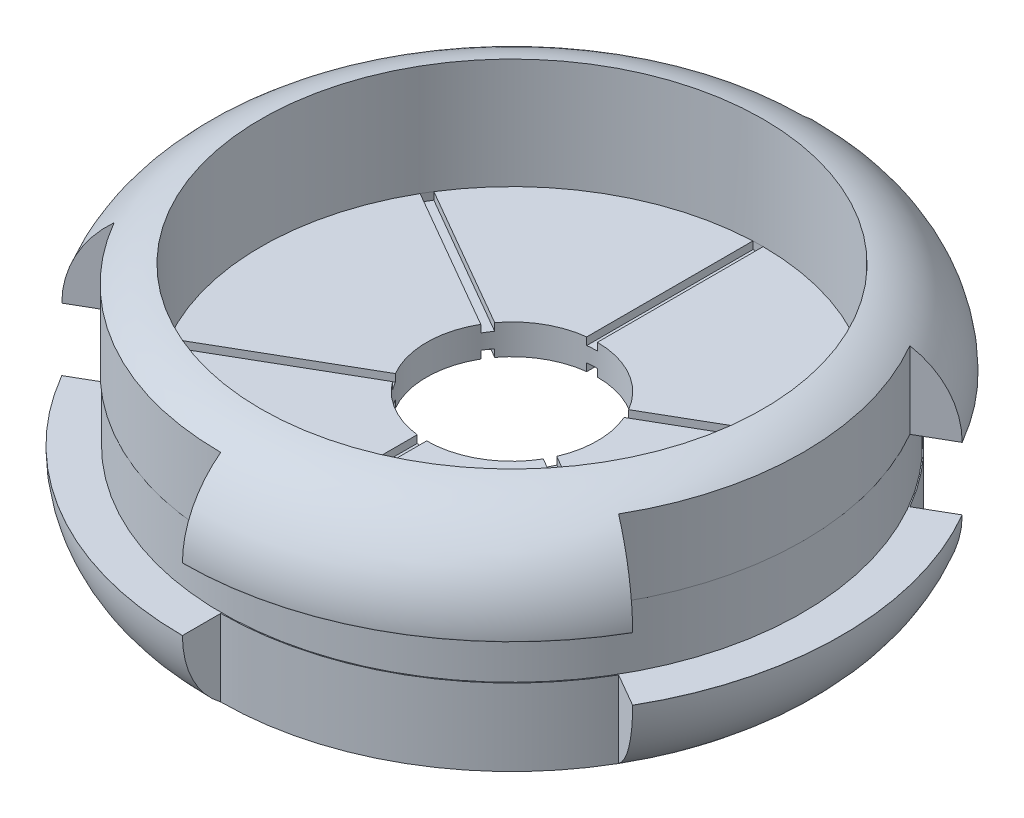
SolidWorks part; units mm, degrees
material "Rubber"
ref_plane "Front" through (0, 0, 0) normal (0, 0, 1) x (1, 0, 0)
ref_plane "Top" through (0, 0, 0) normal (0, 1, 0) x (1, 0, 0)
ref_plane "Right" through (0, 0, 0) normal (1, 0, 0) x (0, 0, -1)
sketch "Sketch1" plane through (0, 0, 0) normal (0, 0, 1) x (1, 0, 0)
  line L0 (-8.3344, 3.175) -> (8.3344, 3.175) construction
  line L1 (0, -3.175) -> (0, 3.175) construction
  line L2 (6.35, 0.7937) -> (6.35, -0.7937) construction
  line L3 (-8.3344, -3.175) -> (8.3344, -3.175) construction
  line L4 (-6.35, 0) -> (6.35, 0) construction
  dimension "flange dia" = 16.6687
  dimension "oall ht" = 6.35
  dimension "D1" = 1.5875
  dimension "for hole dia" = 12.7
sketch "Sketch2" plane through (0, 0, 0) normal (0, 0, 1) x (1, 0, 0)
  line L0 (8.3344, 3.175) -> (8.3344, 0.7938)
  line L1 (8.3344, 3.175) -> (6.35, 3.175)
  line L2 (-8.3344, 3.175) -> (8.3344, 3.175) construction
  line L3 (8.3344, 0.7938) -> (7.3422, 0.7937)
  line L4 (7.3422, 0.7937) -> (7.3422, -0.7937)
  line L5 (7.3422, -0.7937) -> (8.3344, -0.7938)
  line L6 (8.3344, -0.7938) -> (8.3344, -3.175)
  line L7 (8.3344, -3.175) -> (6.35, -3.175)
  line L8 (-8.3344, -3.175) -> (8.3344, -3.175) construction
  line L9 (6.35, -3.175) -> (6.35, 3.175)
  line L10 (6.35, 0.7937) -> (6.35, -0.7937) construction
  line L11 (-6.35, 0) -> (6.35, 0) construction
  point P8 (7.3422, 0)
  dimension "D1" = 0.9922
revolve "Revolve1" add sketch "Sketch2" angle 360 about L1
sketch "Sketch3" plane through (0, 0, 0) normal (0, 1, 0) x (1, 0, 0)
  circle A0 centre (0, 0) radius 6.35
  circle A1 centre (0, 0) radius 2.159
  dimension "D1" = 4.318
extrude "Boss-Extrude1" add sketch "Sketch3" along normal blind 0.381 and the other way blind 0.381
fillet "Fillet1" radius 2.413 2 edges at (0, -3.175, -8.3344) (0, 3.175, -8.3344)
ref_plane "Plane1" through (0, 3.175, 0) normal (0, -1, 0) x (1, 0, 0)
sketch "Sketch4" plane through (0, 3.175, 0) normal (0, -1, 0) x (1, 0, 0)
  line L0 (0, 0) -> (20.1244, 11.6188) construction
  line L1 (20.1244, 11.6188) -> (20.1244, -11.6188) construction
  line L2 (20.1244, -11.6188) -> (0, 0) construction
  line L4 (6.3791, 3.683) -> (7.2178, 4.1672)
  line L5 (6.3791, -3.683) -> (7.2178, -4.1672)
  line L6 (-8.3344, 0) -> (8.3344, 0) construction
  arc A0 (6.3791, 3.683) -> (6.3791, -3.683) centre (0, 0) cw
  circle A2 centre (0, 0) radius 8.3344 construction
  arc A3 (7.2178, 4.1672) -> (7.2178, -4.1672) centre (0, 0) cw
  circle A4 centre (0, 0) radius 8.3344 construction
  circle A5 centre (0, 0) radius 6.35 construction
  point P5 (6.35, 0)
  point P21 (7.366, 0)
  dimension "D1" = 1.016
  dimension "D2" = 20.1244
extrude "Cut-Extrude2" cut sketch "Sketch4" along normal up to surface (2.3813 mm away) up to face at (0, 0.7938, -8.3344)
pattern_circular "CirPattern1" count 3 over 360 about axis through (0, 3.175, 0) along (0, -1, 0) of "Cut-Extrude2"
ref_plane "Plane2" through (0, -3.175, 0) normal (0, -1, 0) x (1, 0, 0)
sketch "Sketch5" plane through (0, -3.175, 0) normal (0, -1, 0) x (1, 0, 0)
  line L0 (0, 0) -> (0, 23.2376) construction
  line L1 (0, 23.2376) -> (20.1244, 11.6188) construction
  line L2 (20.1244, 11.6188) -> (0, 0) construction
  line L3 (0, 0) -> (20.1244, 11.6188) construction
  line L4 (0, 8.3344) -> (0, 7.366)
  line L5 (7.2178, 4.1672) -> (6.3791, 3.683)
  line L6 (6.3791, 3.683) -> (7.2178, 4.1672) construction
  arc A0 (0, 7.366) -> (6.3791, 3.683) centre (0, 0) cw
  arc A1 (0, 8.3344) -> (7.2178, 4.1672) centre (0, 0) cw
  arc A2 (6.3791, -3.683) -> (6.3791, 3.683) centre (0, 0) ccw construction
  arc A3 (7.2178, -4.1672) -> (7.2178, 4.1672) centre (0, 0) ccw construction
extrude "Cut-Extrude3" cut sketch "Sketch5" against normal up to vertex (2.3813 mm away) up to point (6.35, -0.7937, 0)
pattern_circular "CirPattern2" count 3 over 360 about axis through (0, -3.175, 0) along (0, -1, 0) of "Cut-Extrude3"
sketch "Sketch6" plane through (0, 0.381, 0) normal (0, 1, 0) x (1, 0, 0)
  line L0 (0, 0) -> (5.4993, 3.175)
  line L1 (20.1244, 11.6188) -> (0, 0) construction
  line L2 (0, 0) -> (20.1244, -11.6188) construction
  line L3 (5.4993, -3.175) -> (0, 0)
  line L4 (5.6263, -2.955) -> (0.508, 0)
  line L5 (0.508, 0) -> (5.6263, 2.955)
  line L6 (5.4993, -3.175) -> (5.6263, -2.955)
  line L7 (5.4993, 3.175) -> (5.6263, 2.955)
  circle A0 centre (0, 0) radius 6.35 construction
  circle A1 centre (0, 0) radius 6.35 construction
  dimension "D1" = 0.254
extrude "Cut-Extrude4" cut sketch "Sketch6" against normal blind 0.1905
pattern_circular "CirPattern3" count 3 over 360 about axis through (0, 3.175, 0) along (0, -1, 0) of "Cut-Extrude4"
mirror "Mirror1" about plane through (0, 0, 0) normal (0, 1, 0) of "CirPattern3"
equation "\"D1@Sketch2\"=(\"flange dia@Sketch1\"-\"for hole dia@Sketch1\")/4"
